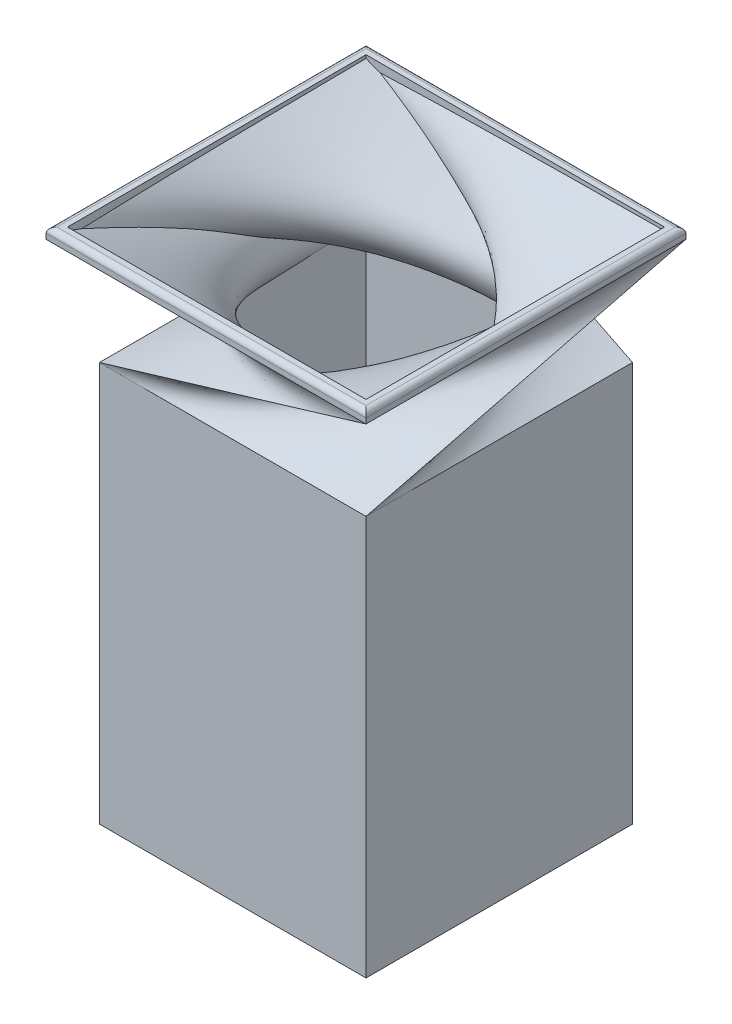
SolidWorks part; units mm, degrees
material "PET"
ref_plane "Front Plane" through (0, 0, 0) normal (0, 0, 1) x (1, 0, 0)
ref_plane "Top Plane" through (0, 0, 0) normal (0, 1, 0) x (1, 0, 0)
ref_plane "Right Plane" through (0, 0, 0) normal (1, 0, 0) x (0, 0, -1)
sketch "Sketch1" plane through (0, 0, 0) normal (0, 1, 0) x (1, 0, 0)
  line L1 (-25, 25) -> (25, 25)
  line L2 (-25, 25) -> (-25, -25)
  line L3 (-25, -25) -> (25, -25)
  line L4 (25, 25) -> (25, -25)
  line L5 (-25, 25) -> (25, -25) construction
  line L6 (-25, -25) -> (25, 25) construction
  point P0 (0, 0)
  dimension "D1" = 50
  dimension "D2" = 50
extrude "Boss-Extrude1" add sketch "Sketch1" along normal blind 75
ref_plane "Plane1" through (0, 95, 0) normal (0, 1, 0) x (1, 0, 0)
sketch "Sketch2" plane through (0, 95, 0) normal (0, 1, 0) x (1, 0, 0)
  line L1 (-30, 30) -> (30, 30)
  line L2 (-30, 30) -> (-30, -30)
  line L3 (-30, -30) -> (30, -30)
  line L4 (30, 30) -> (30, -30)
  line L5 (-30, 30) -> (30, -30) construction
  line L6 (-30, -30) -> (30, 30) construction
  line L11 (-27.5, 27.5) -> (27.5, -27.5) construction
  line L12 (-27.5, -27.5) -> (27.5, 27.5) construction
  point P0 (0, 0)
  point P6 (0, 0)
  dimension "D1" = 60
  dimension "D2" = 60
  dimension "D3" = 55
  dimension "D4" = 55
extrude "Boss-Extrude2" add sketch "Sketch2" along normal blind 2 separate body
loft "Loft1" add section face at (0, 95, 0) section face at (0, 75, 0) connector at (30, 95, 30) connector at (-25, 75, 25)
sketch "Sketch3" plane through (0, 97, 0) normal (0, 1, 0) x (1, 0, 0)
  line L1 (-25, 25) -> (25, 25)
  line L2 (-25, 25) -> (-25, -25)
  line L3 (-25, -25) -> (25, -25)
  line L4 (25, 25) -> (25, -25)
  line L5 (-25, 25) -> (25, -25) construction
  line L6 (-25, -25) -> (25, 25) construction
  point P0 (0, 0)
  dimension "D1" = 50
  dimension "D2" = 50
shell "Shell3" thickness 2 removed face at (0, 97, 0)
fillet "Fillet5" radius 1 4 edges at (30, 97, 0) (0, 97, -30) (-30, 97, 0) (0, 97, 30)
